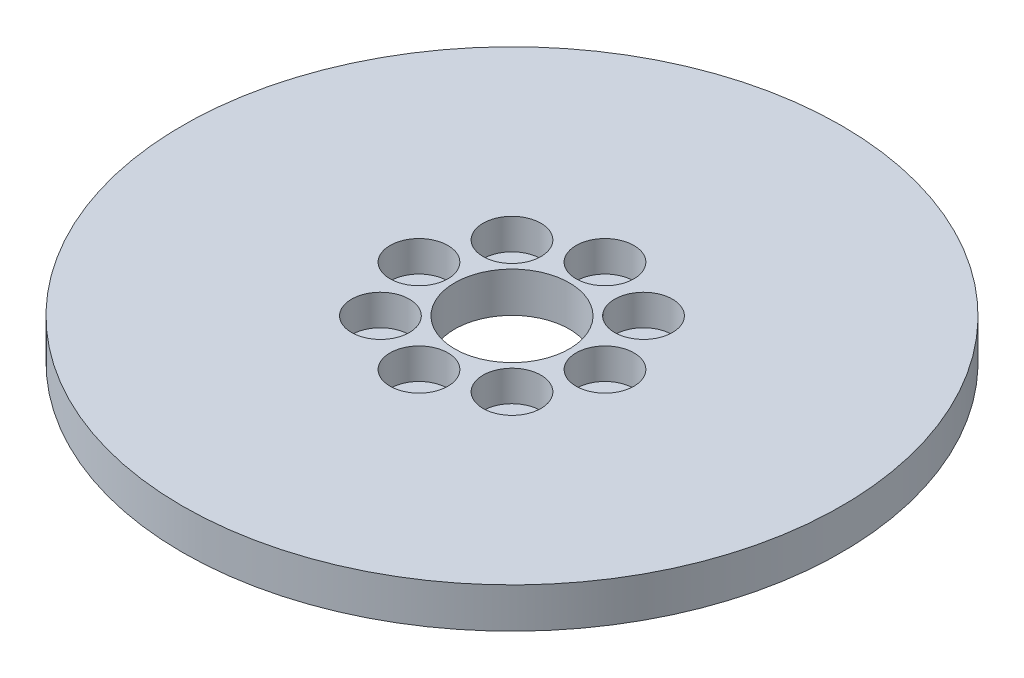
SolidWorks part; units mm, degrees
ref_plane "Front Plane" through (0, 0, 0) normal (0, 0, 1) x (1, 0, 0)
ref_plane "Top Plane" through (0, 0, 0) normal (0, 1, 0) x (1, 0, 0)
ref_plane "Right Plane" through (0, 0, 0) normal (1, 0, 0) x (0, 0, -1)
sketch "Sketch1" plane through (0, 0, 0) normal (0, 1, 0) x (1, 0, 0)
  circle A0 centre (0, 0) radius 57.5
  dimension "FLANGE_OD" = 115
extrude "Boss-Extrude1" add sketch "Sketch1" along normal blind 7
sketch "Sketch2" plane through (0, 0, 0) normal (0, 1, 0) x (1, 0, 0)
  circle A0 centre (0, 0) radius 10
  dimension "BORE_D" = 20
extrude "Cut-Extrude1" cut sketch "Sketch2" along normal through all
sketch "Sketch3" plane through (0, 7, 0) normal (0, 1, 0) x (1, 0, 0)
  circle A0 centre (0, 0) radius 16.2286 construction
  circle A1 centre (-16.2286, 0) radius 5.0469
  dimension "BOLT_D" = 10.0939
  dimension "BOLT_PCD" = 32.4572
extrude "Cut-Extrude2" cut sketch "Sketch3" against normal blind 5.3711
pattern_circular "CirPattern1" count 8 over 360 about axis through (0, 0, 0) along (0, 1, 0) of "Cut-Extrude2"
